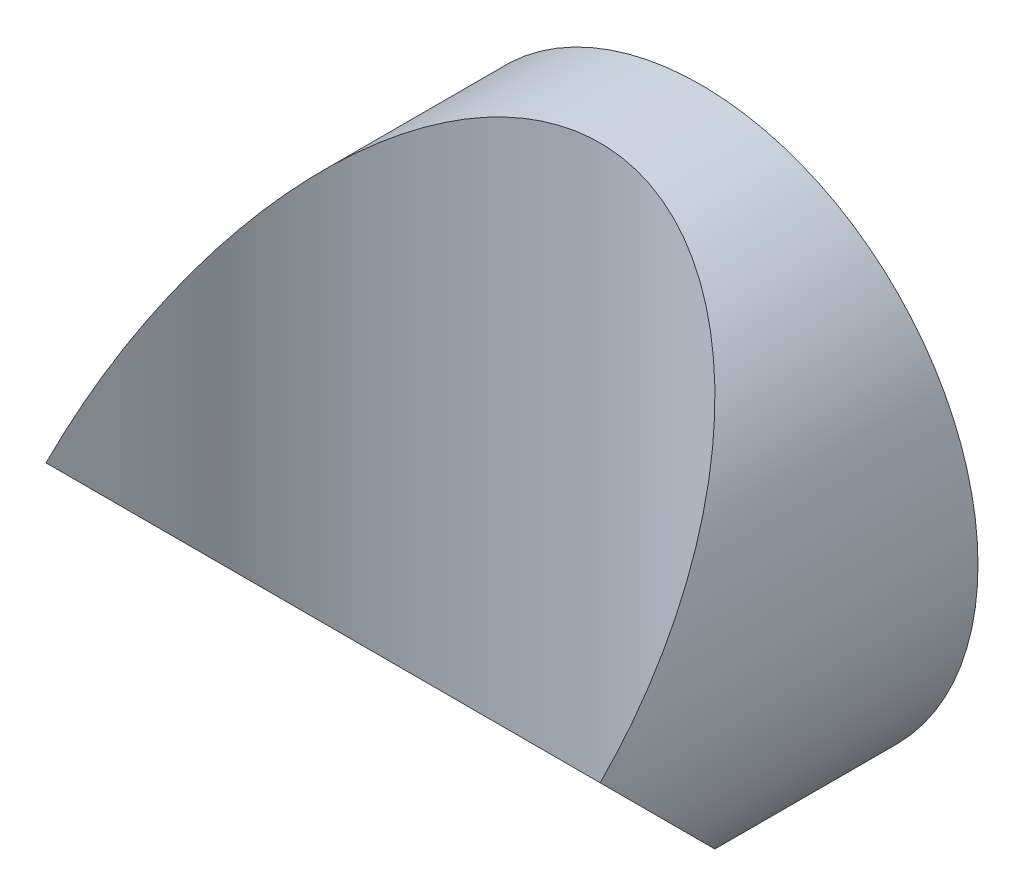
SolidWorks part; units mm, degrees
ref_plane "前视基准面" through (0, 0, 0) normal (0, 0, 1) x (1, 0, 0)
ref_plane "上视基准面" through (0, 0, 0) normal (0, 1, 0) x (1, 0, 0)
ref_plane "右视基准面" through (0, 0, 0) normal (1, 0, 0) x (0, 0, -1)
sketch "草图1" plane through (0, 0, 0) normal (0, 0, 1) x (1, 0, 0)
  circle A0 centre (0, 0) radius 20
extrude "凸台-拉伸1" add sketch "草图1" along normal blind 27.27
sketch "草图2" plane through (0, 0, 0) normal (0, 1, 0) x (1, 0, 0)
  line L1 (-20, -27.27) -> (20, -27.27) construction
  circle A1 centre (0, -27.27) radius 20
extrude "切除-拉伸1" cut sketch "草图2" against normal blind 20 and the other way blind 20
ref_point "点2"
sketch "草图3" plane through (0, 0, 0) normal (0, 0, -1) x (-1, 0, 0)
  line L0 (0, 0) -> (0, 20)
ref_axis "基准轴1" through (0, 0, 18.5529) along (0, 0, -1)
ref_axis "基准轴2" through (0, 0, 0) along (0, 1, 0)
ref_plane "基准面1" through (0, 0, 0) normal (0, 1, 0) x (1, 0, 0)
